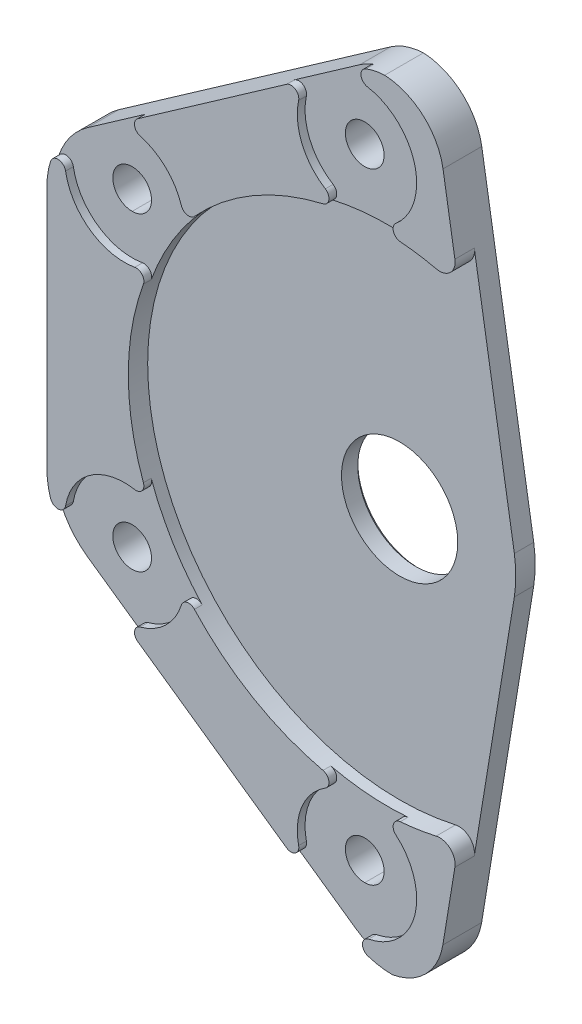
SolidWorks part; units mm, degrees
material "6061-T6 (SS)"
ref_plane "Front Plane" through (0, 0, 0) normal (0, 0, 1) x (1, 0, 0)
ref_plane "Top Plane" through (0, 0, 0) normal (0, 1, 0) x (1, 0, 0)
ref_plane "Right Plane" through (0, 0, 0) normal (1, 0, 0) x (0, 0, -1)
sketch "Sketch1" plane through (0, 0, 0) normal (0, 0, 1) x (1, 0, 0)
  line L0 (18.7988, 3.0832) -> (8.89, 63.5)
  line L1 (8.89, 63.5) -> (-54.61, 63.5)
  line L2 (-54.61, 63.5) -> (-54.61, -63.5)
  line L3 (-54.61, -63.5) -> (8.89, -63.5)
  line L4 (8.89, -63.5) -> (18.7988, -3.0832)
  line L5 (2.54, 0) -> (29.337, 0) construction
  line L6 (8.89, -0.1674) -> (8.89, 46.3356) construction
  line L7 (-54.61, 26.67) -> (-2.0113, 63.5)
  line L9 (-41.91, 25.4) -> (-41.91, 0) construction
  line L11 (-3.81, 50.8) -> (-3.81, -50.8) construction
  line L12 (-54.61, -26.67) -> (-2.0113, -63.5)
  line L13 (-41.91, -25.4) -> (-41.91, 0) construction
  circle A0 centre (0, 0) radius 9.525
  circle A1 centre (0, 0) radius 19.05
  circle A2 centre (-41.91, 25.4) radius 3.175
  circle A3 centre (-3.81, -50.8) radius 3.175
  circle A4 centre (-41.91, -25.4) radius 3.175
  circle A5 centre (-3.81, 50.8) radius 3.175
  point P25 (8.89, 63.5)
  dimension "D2" = 38.1
  dimension "D3" = 19.05
  dimension "D6" = 6.35
  dimension "D7" = 6.35
  dimension "D8" = 38.1
  dimension "D12" = 3.81
  dimension "D11" = 12.7
  dimension "D10" = 50.8
  dimension "D4" = 12.7
  dimension "D5" = 63.5
  dimension "D9" = 101.6
  dimension "D14" = 25.4
  dimension "D15" = 55
  dimension "D16" = 36.83
extrude "Boss-Extrude1" add sketch "Sketch1" along normal blind 6.35 contours A1 L0 L1 L2 L3 L4 A3 A2 | A1 A0 region at (-20.5169, 0, 0) region at (18.4501, 1.5029, 0)
ref_axis "Axis1" through (-41.91, 25.4, 6.35) along (0, 0, -1)
ref_axis "Axis2" through (-3.81, -50.8, 6.35) along (0, 0, -1)
ref_axis "Axis3" through (0, 0, 6.35) along (0, 0, -1)
ref_plane "Plane1" through (-41.91, 0, 0) normal (-1, 0, 0) x (0, 0, 1)
ref_plane "Plane2" through (-3.81, 0, 0) normal (-1, 0, 0) x (0, 0, 1)
split line "Split Line1"
split line "Split Line2"
sketch "Sketch7" plane through (0, 0, 6.35) normal (0, 0, 1) x (1, 0, 0)
  line L0 (-3.81, 50.8) -> (27.31, 50.8) construction
  line L1 (27.31, 50.8) -> (27.31, 78.434)
  line L2 (27.31, 50.8) -> (27.31, -7.6429)
  circle A0 centre (0, 0) radius 9.525
  circle A1 centre (0, 0) radius 12.7
  circle A2 centre (0, 0) radius 41.275
  dimension "D1" = 25.4
  dimension "D2" = 19.05
  dimension "D3" = 31.12
  dimension "D4" = 27.634
  dimension "D5" = 58.4429
  dimension "D6" = 82.55
sketch "Sketch8" plane through (0, 0, 0) normal (0, 0, -1) x (-1, 0, 0)
  circle A0 centre (0, 0) radius 7.11
  circle A1 centre (3.81, 50.8) radius 5.25
  circle A2 centre (41.91, 25.4) radius 5.25
  circle A3 centre (3.81, -50.8) radius 5.25
  circle A4 centre (41.91, -25.4) radius 5.25
  dimension "D1" = 14.22
  dimension "D2" = 10.5
  dimension "D3" = 10.5
  dimension "D4" = 10.5
  dimension "D5" = 10.5
split line "Split Line4"
split line "Split Line5"
sketch "Sketch12" plane through (0, 0, 6.35) normal (0, 0, 1) x (1, 0, 0)
  circle A0 centre (0, 0) radius 41.275
  arc A1 (12.8727, 39.2163) -> (12.8727, -39.2163) centre (0, 0) ccw construction
extrude "Cut-Extrude3" cut sketch "Sketch12" against normal blind 3.175 contours A0
fillet "Fillet3" radius 12.7 2 edges at (-2.0113, -63.5, 3.175) (-54.61, -26.67, 3.175)
fillet "Fillet5" radius 10.16 3 edges at (8.89, 63.5, 3.175) (-2.0113, 63.5, 3.175) (8.89, -63.5, 3.175)
fillet "Fillet6" radius 12.7 1 edges at (-54.61, 26.67, 3.175)
sketch "Sketch13" plane through (0, 0, 0) normal (0, 0, -1) x (-1, 0, 0)
  line L0 (0, 0) -> (7.4717, 0) construction
  line L1 (0.2573, 37.8509) -> (-11.1271, 32.2219)
  line L2 (-11.1271, 32.2219) -> (-0.5601, 25.1772)
  line L3 (-0.5601, 25.1772) -> (0.2573, 37.8509)
  line L4 (3.81, 50.8) -> (41.91, 25.4) construction
  line L5 (18.5208, 46.7586) -> (7.1363, 41.1296)
  line L6 (7.1363, 41.1296) -> (17.7034, 34.0849)
  line L7 (17.7034, 34.0849) -> (18.5208, 46.7586)
  line L14 (6.938, 24.1533) -> (-4.4464, 18.5243)
  line L15 (-4.4464, 18.5243) -> (6.1207, 11.4796)
  line L16 (6.1207, 11.4796) -> (6.938, 24.1533)
  line L17 (25.2015, 33.061) -> (13.8171, 27.432)
  line L18 (13.8171, 27.432) -> (24.3842, 20.3873)
  line L19 (24.3842, 20.3873) -> (25.2015, 33.061)
  circle A0 centre (-3.81, 31.75) radius 3.6662 construction
  dimension "D1" = 12.7
  dimension "D2" = 31.75
  dimension "D3" = 3.81
  dimension "D4" = 2
  dimension "D5" = 2
extrude "Cut-Extrude4" [suppressed] cut sketch "Sketch13" against normal through all contours L2 L3 L1 | L6 L7 L5 | L18 L19 L17 | L15 L16 L14
mirror "Mirror1" [suppressed] about plane through (0, 0, 0) normal (0, 1, 0)
sketch "Sketch14" plane through (0, 0, 0) normal (0, 0, -1) x (-1, 0, 0)
  circle A0 centre (-4.9894, 33.6023) radius 3.81
  circle A1 centre (4.1423, 38.0562) radius 3.81
  circle A2 centre (13.2741, 42.51) radius 3.81
  circle A3 centre (8.5962, 28.9244) radius 3.81
  circle A4 centre (17.7279, 33.3783) radius 3.81
  circle A5 centre (13.05, 19.7927) radius 3.81
  circle A6 centre (22.1818, 24.2465) radius 3.81
  circle A7 centre (-0.5356, 24.4706) radius 3.81
  circle A8 centre (3.9183, 15.3388) radius 3.81
  dimension "D1" = 7.62
  dimension "D2" = 3
extrude "Cut-Extrude5" [suppressed] cut sketch "Sketch14" against normal through all
mirror "Mirror2" [suppressed] about plane through (0, 0, 0) normal (0, 1, 0)
sketch "Sketch15" plane through (0, 0, 0) normal (0, 0, -1) x (-1, 0, 0)
  point P0 (3.81, 50.8)
  point P1 (41.91, 25.4)
  point P3 (41.91, -25.4)
  point P5 (3.81, -50.8)
chamfer "Chamfer1" distance 0.508 angle 45 1 edges at (9.525, 0, 0)
sketch "Sketch16" plane through (0, 0, 6.35) normal (0, 0, 1) x (1, 0, 0)
  circle A0 centre (-3.81, 50.8) radius 9.779
  circle A1 centre (-41.91, 25.4) radius 9.779
  circle A2 centre (-41.91, -25.4) radius 9.779
  circle A3 centre (-3.81, -50.8) radius 9.779
  dimension "D1" = 19.558
extrude "Cut-Extrude6" cut sketch "Sketch16" against normal blind 1.27
fillet "Fillet7" radius 1.27 16 edges at (-1.7648, -41.2373, 5.715) (-4.4059, -41.0392, 5.715) (-6.8971, -60.0789, 5.715) (-11.4735, -56.8745, 5.715) (-32.1434, -25.8926, 5.715) (-42.4818, -35.1623, 5.715) (-37.8274, -16.514, 5.715) (-51.0503, -28.8761, 5.715) (-4.4059, 41.0392, 5.715) (-11.4735, 56.8745, 5.715) (-37.8274, 16.514, 5.715) (-51.0503, 28.8761, 5.715) (-32.1434, 25.8926, 5.715) (-42.4818, 35.1623, 5.715) (-1.7648, 41.2373, 5.715) (-6.8971, 60.0789, 5.715)
fillet "Fillet8" radius 2.54 2 edges at (12.8727, -39.2163, 4.7625) (12.8727, 39.2163, 4.7625)
